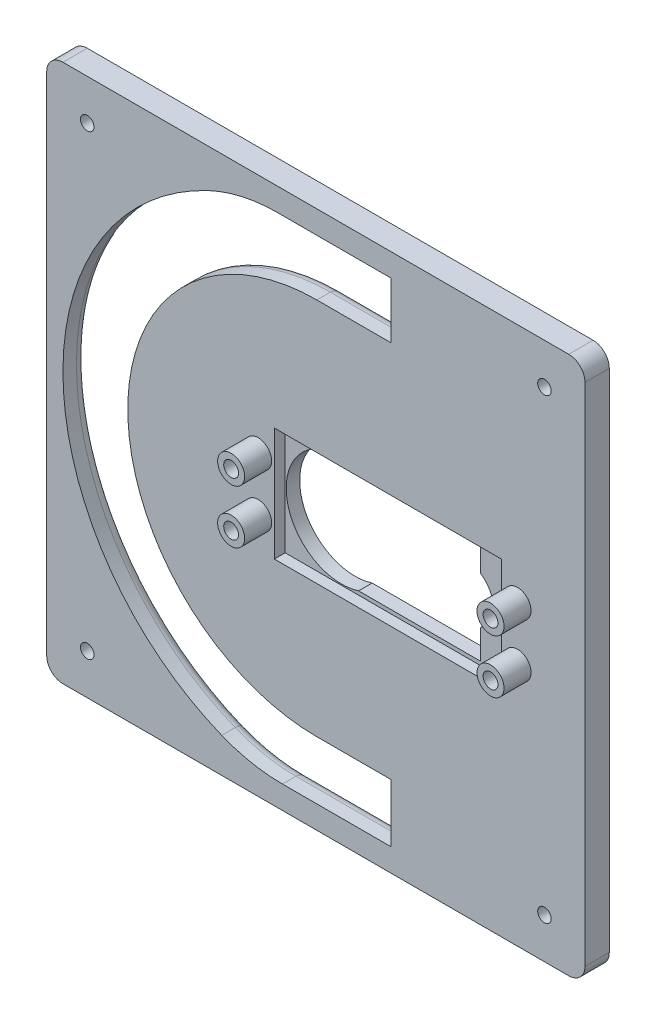
SolidWorks part; units mm, degrees
ref_plane "Front Plane" through (0, 0, 0) normal (0, 0, 1) x (1, 0, 0)
ref_plane "Top Plane" through (0, 0, 0) normal (0, 1, 0) x (1, 0, 0)
ref_plane "Right Plane" through (0, 0, 0) normal (1, 0, 0) x (0, 0, -1)
sketch "Sketch1" plane through (0, 0, 0) normal (0, 0, 1) x (1, 0, 0)
  line L1 (-74.75, 49.6) -> (24.85, 49.6)
  line L2 (-74.75, 49.6) -> (-74.75, -50)
  line L3 (-74.75, -50) -> (24.85, -50)
  line L4 (24.85, 49.6) -> (24.85, -50)
  line L6 (-30.65, 0.0012) -> (-33.35, 0.0012) construction
  line L7 (-15.8956, -0.0011) -> (-5.4456, -0.0011) construction
  circle A0 centre (-22.1047, 0) radius 7.5
  dimension "D3" = 15
  dimension "D8" = 2.7
  dimension "D1" = 99.6
  dimension "D2" = 99.6
  dimension "D5" = 74.75
  dimension "D6" = 50
extrude "Boss-Extrude1" add sketch "Sketch1" along normal blind 3 and the other way blind 1.5
sketch "Sketch20" plane through (0, 0, -1.5) normal (0, 0, -1) x (-1, 0, 0)
  line L0 (-24.85, 49.6) -> (74.75, 49.6) construction
  line L1 (11.0318, 45.36) -> (32.0349, 45.36)
  line L2 (24.75, 35) -> (11.0318, 35)
  line L3 (11.0318, 35) -> (11.0318, 45.36)
  line L4 (11.0318, -45.76) -> (31.1236, -45.76)
  line L5 (24.75, -35) -> (11.0318, -35)
  line L6 (11.0318, -35) -> (11.0318, -45.76)
  line L8 (74.75, -50) -> (-24.85, -50) construction
  arc A0 (42.371, -43.5718) -> (44.8907, 42.4659) centre (24.75, 0) ccw
  arc A1 (24.75, -35) -> (24.75, 35) centre (24.75, 0) ccw
  circle A2 centre (24.75, 0) radius 47 construction
  circle A3 centre (24.75, 0) radius 35 construction
  arc A4 (32.0349, 45.36) -> (44.8907, 42.4659) centre (32.0349, 15.36) cw
  arc A5 (31.1236, -45.76) -> (42.371, -43.5718) centre (31.1236, -15.76) ccw
  dimension "D2" = 24.75
  dimension "D4" = 10.36
  dimension "D6" = 49.6
  dimension "D1" = 35
  dimension "D8" = 30
  dimension "D10" = 30
  dimension "D5" = 10.76
  dimension "D7" = 4.24
  dimension "D9" = 4.24
  dimension "D3" = 12
extrude "Cut-Extrude13" cut sketch "Sketch20" against normal up to surface (4.5 mm away) contours A1 A0 region at (-21.5334, 44.265, -1.5) up to face at (-24.95, -0.2, 3)
sketch "Sketch38" plane through (0, 0, 3) normal (0, 0, 1) x (1, 0, 0)
  line L0 (-22.1047, 0) -> (-36.6047, 0) construction
  circle A0 centre (-35.6241, 5) radius 1.375
  circle A1 centre (-35.6241, -4.9029) radius 1.375
  circle A2 centre (-35.6241, -4.9029) radius 2.5
  circle A3 centre (-35.6241, 5) radius 2.5
  circle A4 centre (12.3759, 5) radius 1.375
  circle A5 centre (12.3759, 5) radius 2.5
  circle A6 centre (12.3759, -4.9029) radius 1.375
  circle A7 centre (12.3759, -4.9029) radius 2.5
  dimension "D1" = 5
  dimension "D3" = 2.75
  dimension "D4" = 2.75
  dimension "D5" = 5
  dimension "D6" = 5
  dimension "D7" = 48
  dimension "D9" = 5
  dimension "D10" = 2.75
  dimension "D11" = 2.75
  dimension "D12" = 5
  dimension "D2" = 5
  dimension "D8" = 48
extrude "Boss-Extrude12" add sketch "Sketch38" along normal blind 5
sketch "Sketch42" plane through (0, 0, -1.5) normal (0, 0, -1) x (-1, 0, 0)
  line L0 (-3.0577, 9.75) -> (19.03, 9.75)
  line L1 (-3.0577, -9.75) -> (19.03, -9.75)
  line L2 (-3.0577, 9.75) -> (-3.0577, 4.2426)
  line L3 (-3.0577, -4.2426) -> (-3.0577, -9.75)
  arc A0 (19.03, -9.75) -> (19.03, 9.75) centre (22.1923, 0) ccw
  arc A1 (-3.0577, 4.2426) -> (-3.0577, -4.2426) centre (0.4423, 0) ccw
  dimension "D2" = 0.4423
  dimension "D3" = 5.5
  dimension "D4" = 9.75
  dimension "D7" = 10.25
  dimension "D1" = 3.0577
  dimension "D5" = 9.75
  dimension "D6" = 19.5
  dimension "D8" = 22.0877
  dimension "D9" = 22.0877
extrude "Cut-Extrude35" cut sketch "Sketch42" against normal blind 10 contours L2 A1 L3 L1 A0 L0 region at (-13.5402, 0, -1.5)
sketch "Sketch43" plane through (0, 0, -1.5) normal (0, 0, -1) x (-1, 0, 0)
  line L0 (-3.0577, -9.75) -> (-3.5577, -9.75)
  line L1 (-3.5577, -9.75) -> (-3.5577, -4.2963)
  line L2 (-3.0577, 9.75) -> (-3.5577, 9.75)
  line L3 (-3.5577, 9.75) -> (-3.5577, 4.2963)
  line L4 (-3.0577, 9.75) -> (-3.0577, 4.5853)
  line L5 (-3.0577, 4.5853) -> (-3.0577, -4.5853)
  line L6 (-3.0577, -4.2426) -> (-3.0577, -9.75) construction
  line L7 (-3.0577, -4.5853) -> (-3.0577, -9.75)
  arc A0 (-3.5577, 4.2963) -> (-3.5577, -4.2963) centre (-0.7407, 0) ccw
  dimension "D1" = 5.1375
  dimension "D2" = 0.7407
  dimension "D5" = 9.75
  dimension "D3" = 0.5
  dimension "D4" = 0.5
  dimension "D6" = 5.1647
  dimension "D7" = 5.1647
extrude "Cut-Extrude36" cut sketch "Sketch43" against normal up to surface (4.5 mm away) up to face at (-6.2069, 0, 3)
sketch "Sketch44" plane through (0, 0, 3) normal (0, 0, 1) x (1, 0, 0)
  circle A0 centre (12.3759, -4.9029) radius 1.5
  circle A1 centre (12.3759, 5) radius 1.5
  circle A2 centre (-35.6241, 5) radius 1.5
  circle A3 centre (-35.6241, -4.9029) radius 1.5
extrude "Cut-Extrude37" cut sketch "Sketch44" against normal blind 2
hole_wizard "M3x0.5 Tapped Hole1" positions "Sketch45" profile "Sketch47" tap size "M3x0.5" standard "ANSI Metric" end condition through all
sketch "Sketch45" plane through (0, 0, -1.5) normal (0, 0, -1) x (-1, 0, 0)
  line L0 (-24.85, -50) -> (-24.85, 49.6) construction
  line L1 (-24.85, 49.6) -> (74.75, 49.6) construction
  line L2 (74.75, 49.6) -> (74.75, -50) construction
  line L3 (74.75, -50) -> (-24.85, -50) construction
  point P0 (-17.35, 42.1)
  point P2 (-17.35, -42.5)
  point P4 (67.25, -42.5)
  point P6 (67.25, 42.1)
  dimension "D1" = 7.5
  dimension "D2" = 7.5
  dimension "D3" = 7.5
  dimension "D4" = 7.5
  dimension "D5" = 7.5
  dimension "D6" = 7.5
  dimension "D7" = 7.5
  dimension "D8" = 7.5
sketch "Sketch47" plane through (17.35, 42.1, -1.5) normal (1, 0, 0) x (0, 1, 0)
  line L0 (0, 0) -> (0, 9.5)
  line L1 (0, 9.5) -> (1.25, 9.5)
  line L2 (1.25, 9.5) -> (1.25, 0)
  line L5 (1.25, 0) -> (0, 0)
  line L11 (0, -6.35) -> (0, 107.95) construction
  dimension "Thru Tap Drill Dia." = 2.5
  dimension "Thru Tap Drill Depth" = 9.5
cosmetic thread "Hole Thread1" parameters "D2"=3
cosmetic thread "Hole Thread2" parameters "D2"=3
cosmetic thread "Hole Thread3" parameters "D2"=3
cosmetic thread "Hole Thread4" parameters "D2"=3
fillet "Fillet1" radius 3 4 edges at (24.85, 49.6, 0.75) (24.85, -50, 0.75) (-74.75, -50, 0.75) (-74.75, 49.6, 0.75)
fillet "Fillet3" radius 2 10 edges at (-17.8909, -35, -1.5) (-59.75, 0, -1.5) (-21.0777, -45.76, -1.5) (-36.8528, -45.2079, -1.5) (-71.7299, -1.3758, -1.5) (-38.6237, 44.6275, -1.5) (-11.0318, -40.38, -1.5) (-17.8909, 35, -1.5) (-11.0318, 40.18, -1.5) (-21.5334, 45.36, -1.5)
sketch "Sketch48" plane through (0, 0, 3) normal (0, 0, 1) x (1, 0, 0)
  line L0 (-35.6241, 5) -> (12.3759, -4.9029) construction
  line L2 (-32.6241, 10.5485) -> (9.3759, 10.5485)
  line L3 (-32.6241, 10.5485) -> (-32.6241, -10.4515)
  line L4 (-32.6241, -10.4515) -> (9.3759, -10.4515)
  line L5 (9.3759, 10.5485) -> (9.3759, -10.4515)
  line L6 (-32.6241, 10.5485) -> (9.3759, -10.4515) construction
  line L7 (-32.6241, -10.4515) -> (9.3759, 10.5485) construction
  point P4 (-11.6241, 0.0485)
  dimension "D1" = 21
  dimension "D2" = 42
extrude "Cut-Extrude38" cut sketch "Sketch48" against normal blind 2
